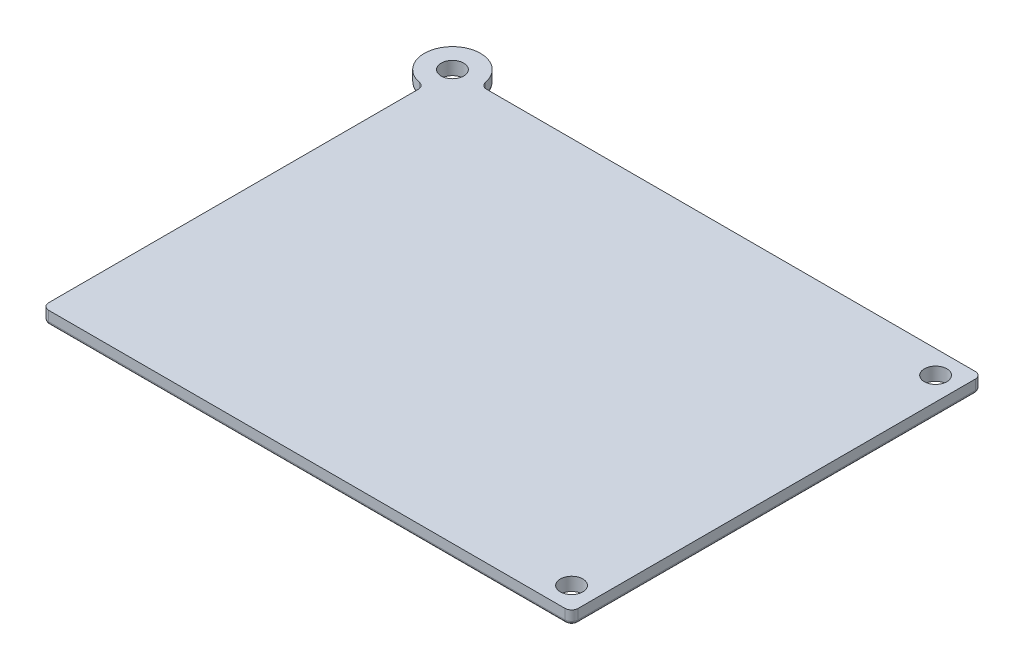
SolidWorks part; units mm, degrees
material "PVC Rigid"
ref_plane "Front Plane" through (0, 0, 0) normal (0, 0, 1) x (1, 0, 0)
ref_plane "Top Plane" through (0, 0, 0) normal (0, 1, 0) x (1, 0, 0)
ref_plane "Right Plane" through (0, 0, 0) normal (1, 0, 0) x (0, 0, -1)
sketch "Sketch1" plane through (0, 0, 0) normal (0, 1, 0) x (1, 0, 0)
  line L1 (-40, -31) -> (40, -31)
  line L2 (-40, -31) -> (-40, 25.8461)
  line L3 (-34.8461, 31) -> (40, 31)
  line L4 (40, -31) -> (40, 31)
  line L5 (-40, -31) -> (40, 31) construction
  line L6 (0, 0) -> (40, -31) construction
  arc A0 (-40, 25.8461) -> (-40.8095, 26.8278) centre (-41, 25.8461) ccw construction
  arc A1 (-35.8278, 31.8095) -> (-34.8461, 31) centre (-34.8461, 32) ccw construction
  arc A2 (-35.8278, 31.8095) -> (-40.8095, 26.8278) centre (-40, 31) ccw construction
  arc A3 (-40, 25.8461) -> (-40.8095, 26.8278) centre (-41, 25.8461) ccw
  arc A4 (-35.8278, 31.8095) -> (-34.8461, 31) centre (-34.8461, 32) ccw
  arc A5 (-35.8278, 31.8095) -> (-40.8095, 26.8278) centre (-40, 31) ccw
  point P0 (0, 0)
  dimension "D1" = 80
  dimension "D2" = 62
extrude "Main Body" add sketch "Sketch1" along normal blind 2
fillet "Corners" radius 1 3 edges at (-40, 1, 31) (40, 1, -31) (40, 1, 31)
fillet "Edge" radius 0.5 10 edges at (-39.7071, 0, 30.7071) (39.7071, 0, -30.7071) (39.7071, 0, 30.7071) (-40, 0, 2.0769) (2.0769, 0, -31) (40, 0, 0) (0, 0, 31) (-40.2285, 0, -26.4823) (-43.0052, 0, -34.0052) (-35.4823, 0, -31.2285)
sketch "Sketch7" plane through (0, 0, 0) normal (0, -1, 0) x (-1, 0, 0)
  line L0 (-39, 31) -> (34.8461, 31) construction
  line L1 (-40, -30) -> (-40, 30) construction
  line L2 (39, -31) -> (-39, -31) construction
  circle A0 centre (-36.5, 27.5) radius 1.7
  circle A1 centre (-36.5, -27.5) radius 1.7
  arc A2 (40.7143, 27.3187) -> (36.3187, 31.7143) centre (40, 31) ccw construction
  circle A4 centre (40, 31) radius 1.7
  point P9 (0, 0)
  point P14 (0, 0)
  point P15 (0, 0)
  point P16 (0, 0)
  dimension "D3" = 3.4
  dimension "D4" = 3.4
  dimension "D6" = 3.4
  dimension "D1" = 3.5
  dimension "D2" = 3.5
  dimension "D5" = 3.5
extrude "Lid Holes" cut sketch "Sketch7" against normal through all both and the other way through all
sketch "CHANGE ME TO ALTER PEG ANGLE" plane through (0, 0, 0) normal (0, -1, 0) x (-1, 0, 0)
  line L0 (39.5, -30) -> (25.9753, -15.2663) construction
  line L1 (-39.3536, -30.3536) -> (-25.6372, -15.7981) construction
  line L2 (-39.5, 30) -> (-39.5, -30) construction
  line L3 (40, 25.8461) -> (40, -30) construction
  arc A0 (-39.5, -30) -> (-39, -30.5) centre (-39, -30) ccw construction
  point P8 (-21.5086, -11.0955)
  dimension "D1" = 43.3
  dimension "D2" = 20
  dimension "D3" = 20
  dimension "D4" = 42.55
sketch "Sketch4" plane through (0, 0, 0) normal (0, -1, 0) x (-1, 0, 0)
  line L0 (-39.3536, -30.3536) -> (-25.6372, -15.7981) construction
  line L3 (-34.7206, -19.6048) -> (-28.8985, -25.0913) construction
  circle A0 centre (-34.7206, -19.6048) radius 2.325
  circle A1 centre (-28.8985, -25.0913) radius 2.325
  point P8 (-31.8096, -22.3481)
  dimension "D1" = 4.65
  dimension "D3" = 4.65
  dimension "D2" = 4
  dimension "D4" = 8
  dimension "D5" = 11
extrude "Boss-Extrude3" add sketch "Sketch4" along normal blind 1.6
fillet "Fillet3" radius 0.05 2 edges at (34.7206, -1.6, 17.2798) (28.8985, -1.6, 22.7663)
pattern_linear "LPattern5" count 4 spacing 8 along (-0.6858, 0, -0.7278) of "Boss-Extrude3", "Fillet3"
sketch "Sketch9" plane through (0, 0, 0) normal (0, -1, 0) x (-1, 0, 0)
  line L0 (39.5, -30) -> (25.9753, -15.2663) construction
  line L2 (28.2092, -23.6149) -> (34.1027, -18.2051) construction
  circle A0 centre (28.2092, -23.6149) radius 2.325
  circle A1 centre (34.1027, -18.2051) radius 2.325
  arc A2 (39, -31) -> (40, -30) centre (39, -30) ccw construction
  point P8 (31.1559, -20.91)
  point P11 (39.7071, -30.7071)
  dimension "D1" = 4.65
  dimension "D2" = 4.65
  dimension "D3" = 8
  dimension "D4" = 13
extrude "Pegs (Diagonal)" add sketch "Sketch9" along normal blind 1.6
fillet "Fillet6" radius 0.05 2 edges at (-28.2092, -1.6, 21.2899) (-34.1027, -1.6, 15.8801)
pattern_linear "LPattern6" count 4 spacing 8 along (0.6762, 0, -0.7367) of "Pegs (Diagonal)"
sketch "Alignment points" plane through (0, 0, 0) normal (0, -1, 0) x (-1, 0, 0)
  line L0 (-23.7475, -7.9604) -> (-17.9254, -13.447) construction
  line L1 (-29.2341, -13.7826) -> (-23.4119, -19.2691) construction
  line L2 (-26.323, -16.5259) -> (-20.8365, -10.7037) construction
  line L3 (23.283, -6.4181) -> (17.3895, -11.8279) construction
  line L4 (28.6928, -12.3116) -> (22.7993, -17.7214) construction
  line L5 (20.3362, -9.123) -> (25.7461, -15.0165) construction
  point P0 (-23.5797, -13.6148)
  point P1 (23.0411, -12.0697)
  point P12 (-23.5797, -13.6148)
  point P23 (23.0411, -12.0697)
sketch "Alignment points streamlined" plane through (0, 0, 0) normal (0, -1, 0) x (-1, 0, 0)
  point P0 (-23.5797, -13.6148)
  point P1 (23.0411, -12.0697)
equation "\"D2@Sketch9\"=\"D1@Sketch9\""
equation "\"D3@Sketch4\"=\"D1@Sketch4\""
equation "\"D4@Sketch4\"=\"D2@Sketch4\"*2"
equation "\"D4@Sketch7\"=\"D3@Sketch7\""
equation "\"D5@Sketch7\"=\"D1@Sketch7\""
equation "\"D6@Sketch7\"=\"D3@Sketch7\""
